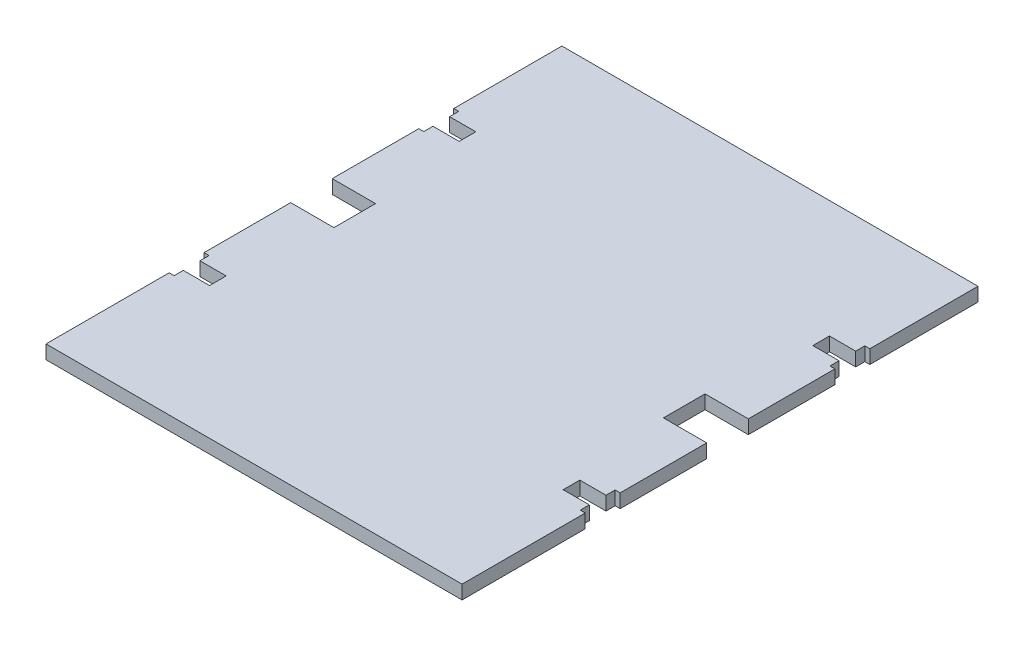
SolidWorks part; units mm, degrees
ref_plane "Front Plane" through (0, 0, 0) normal (0, 0, 1) x (1, 0, 0)
ref_plane "Top Plane" through (0, 0, 0) normal (0, 1, 0) x (1, 0, 0)
ref_plane "Right Plane" through (0, 0, 0) normal (1, 0, 0) x (0, 0, -1)
sketch "Sketch1" plane through (0, 0, 0) normal (0, 1, 0) x (1, 0, 0)
  line L1 (-250, -310) -> (250, -310)
  line L2 (-250, -310) -> (-250, 310)
  line L3 (-250, 310) -> (250, 310)
  line L4 (250, -310) -> (250, 310)
  line L5 (-250, -310) -> (250, 310) construction
  line L6 (-250, 310) -> (250, -310) construction
  point P0 (0, 0)
  dimension "D1" = 500
  dimension "D2" = 620
extrude "Boss-Extrude1" add sketch "Sketch1" along normal blind 16.5
sketch "Sketch2" plane through (0, 16.5, 0) normal (0, 1, 0) x (1, 0, 0)
  line L0 (-250, 310) -> (-250, -310) construction
  line L1 (-250, 34) -> (-198, 34)
  line L2 (-250, 34) -> (-250, -16)
  line L3 (-250, -16) -> (-198, -16)
  line L4 (-198, 34) -> (-198, -16)
  line L5 (250, -310) -> (250, 310) construction
  line L6 (250, 34) -> (198, 34)
  line L7 (250, 34) -> (250, -16)
  line L8 (250, -16) -> (198, -16)
  line L9 (198, 34) -> (198, -16)
  line L10 (250, 310) -> (-250, 310) construction
  line L11 (0, 310) -> (0, -310) construction
  line L12 (-250, 180) -> (-244, 180)
  line L13 (-250, 180) -> (-250, 138)
  line L14 (-250, 138) -> (-244, 138)
  line L15 (-244, 180) -> (-244, 169)
  line L16 (-244, 169) -> (-212.5, 169)
  line L18 (-244, 149) -> (-212.5, 149)
  line L19 (-212.5, 169) -> (-212.5, 149)
  line L20 (-250, -310) -> (250, -310) construction
  line L21 (-92.6056, 0) -> (108.2015, 0) construction
  line L22 (212.5, 169) -> (212.5, 149)
  line L23 (244, 149) -> (212.5, 149)
  line L25 (244, 169) -> (212.5, 169)
  line L26 (244, 180) -> (244, 169)
  line L27 (250, 138) -> (244, 138)
  line L28 (250, 180) -> (250, 138)
  line L29 (250, 180) -> (244, 180)
  line L46 (212.5, -131) -> (212.5, -151)
  line L47 (-250, -120) -> (-244, -120)
  line L48 (-250, -120) -> (-250, -162)
  line L49 (-250, -162) -> (-244, -162)
  line L50 (-244, -120) -> (-244, -131)
  line L51 (-244, -131) -> (-212.5, -131)
  line L53 (-244, -151) -> (-212.5, -151)
  line L54 (-212.5, -131) -> (-212.5, -151)
  line L55 (244, -151) -> (212.5, -151)
  line L57 (244, -131) -> (212.5, -131)
  line L58 (244, -120) -> (244, -131)
  line L59 (250, -162) -> (244, -162)
  line L60 (250, -120) -> (250, -162)
  line L61 (250, -120) -> (244, -120)
  line L62 (-244, 149) -> (-244, 138)
  line L63 (244, 149) -> (244, 138)
  line L64 (244, -151) -> (244, -162)
  line L65 (-244, -151) -> (-244, -162)
  dimension "D1" = 276
  dimension "D2" = 50
  dimension "D3" = 52
  dimension "D4" = 52
  dimension "D5" = 50
  dimension "D6" = 276
  dimension "D7" = 130
  dimension "D8" = 42
  dimension "D9" = 6
  dimension "D10" = 31.5
  dimension "D11" = 20
  dimension "D12" = 6
  dimension "D13" = 42
  dimension "D14" = 31.5
  dimension "D15" = 20
  dimension "D16" = 148
extrude "Cut-Extrude1" cut sketch "Sketch2" against normal through all
